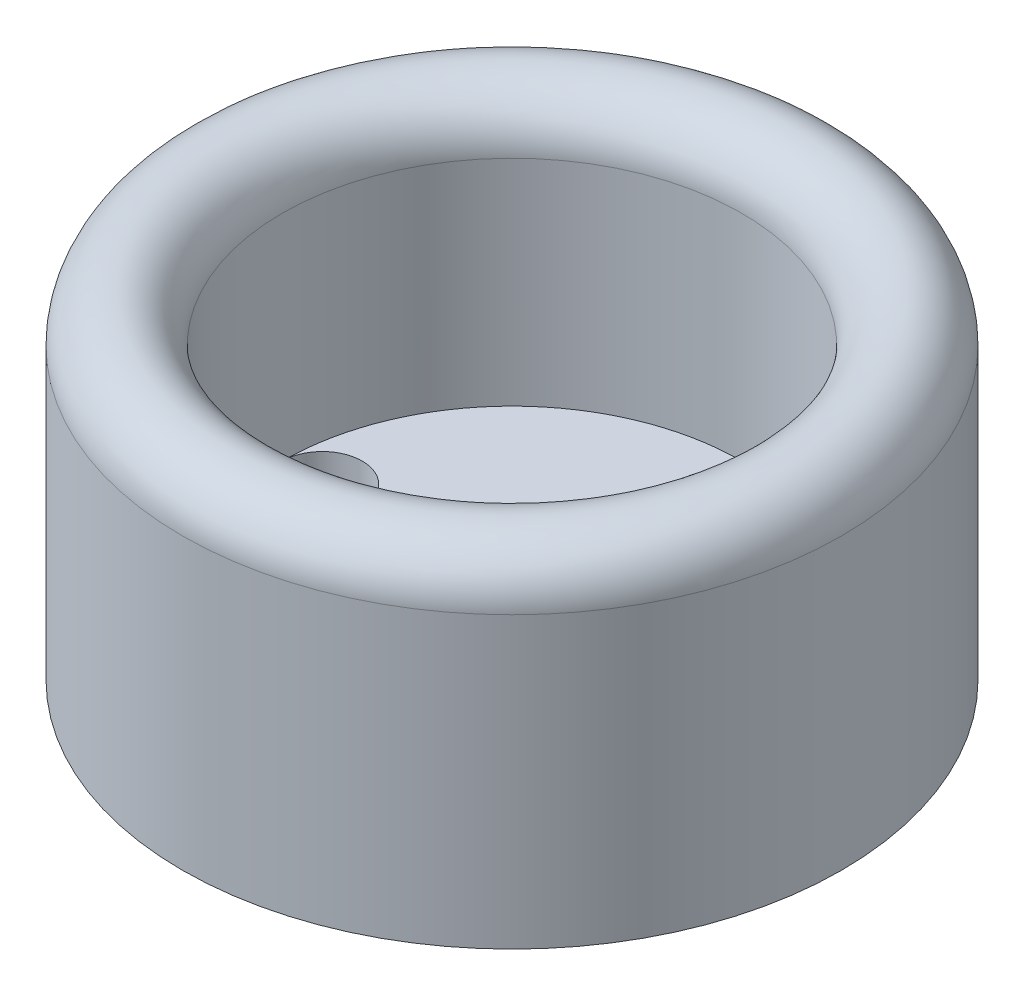
SolidWorks part; units mm, degrees
ref_plane "Front Plane" through (0, 0, 0) normal (0, 0, 1) x (1, 0, 0)
ref_plane "Top Plane" through (0, 0, 0) normal (0, 1, 0) x (1, 0, 0)
ref_plane "Right Plane" through (0, 0, 0) normal (1, 0, 0) x (0, 0, -1)
sketch "Sketch1" plane through (0, 0, 0) normal (0, 1, 0) x (1, 0, 0)
  line L1 (-29, -29) -> (29, -29) construction
  line L2 (-29, -29) -> (-29, 29) construction
  line L3 (-29, 29) -> (29, 29) construction
  line L4 (29, -29) -> (29, 29) construction
  line L5 (0, 29) -> (0, -29) construction
  line L6 (-29, 0) -> (29, 0) construction
  circle A0 centre (-19, 0) radius 1.8
  circle A1 centre (19, 0) radius 1.8
  circle A4 centre (0, 0) radius 5.5
  circle A5 centre (0, 0) radius 25
  point P0 (0, 0)
  dimension "D3" = 3.6
  dimension "D5" = 10
  dimension "D6" = 11
  dimension "D2" = 50
  dimension "D1" = 58
extrude "Boss-Extrude1" add sketch "Sketch1" along normal blind 7.5
sketch "Sketch2" plane through (0, 7.5, 0) normal (0, 1, 0) x (1, 0, 0)
  circle A4 centre (-19, 0) radius 4
  circle A5 centre (19, 0) radius 4
  dimension "D1" = 8
  dimension "D2" = 8
extrude "Cut-Extrude1" cut sketch "Sketch2" against normal blind 6
sketch "Sketch3" plane through (0, 0, 0) normal (0, -1, 0) x (1, 0, 0)
  circle A0 centre (0, 0) radius 33
  circle A1 centre (0, 0) radius 23
  circle A2 centre (-19, 0) radius 4 construction
  dimension "D1" = 10
extrude "Boss-Extrude2" add sketch "Sketch3" against normal blind 26.5 from surface starting at face at (-19, 7.5, 4)
fillet "Fillet1" 2 edges at (0, 34, 33) (0, 34, 23) type full round first side face at (0, 34, 33) second side face at (0, 34, 23) middle face at (0, 34, 33)
extrude "Boss-Extrude3" add sketch "Sketch3<2>" against normal up to surface (7.5 mm away) up to face at (0, 7.5, 5.5)
sketch "Sketch3<2>" plane through (0, 0, 0) normal (0, -1, 0) x (1, 0, 0) same geometry as "Sketch3"
